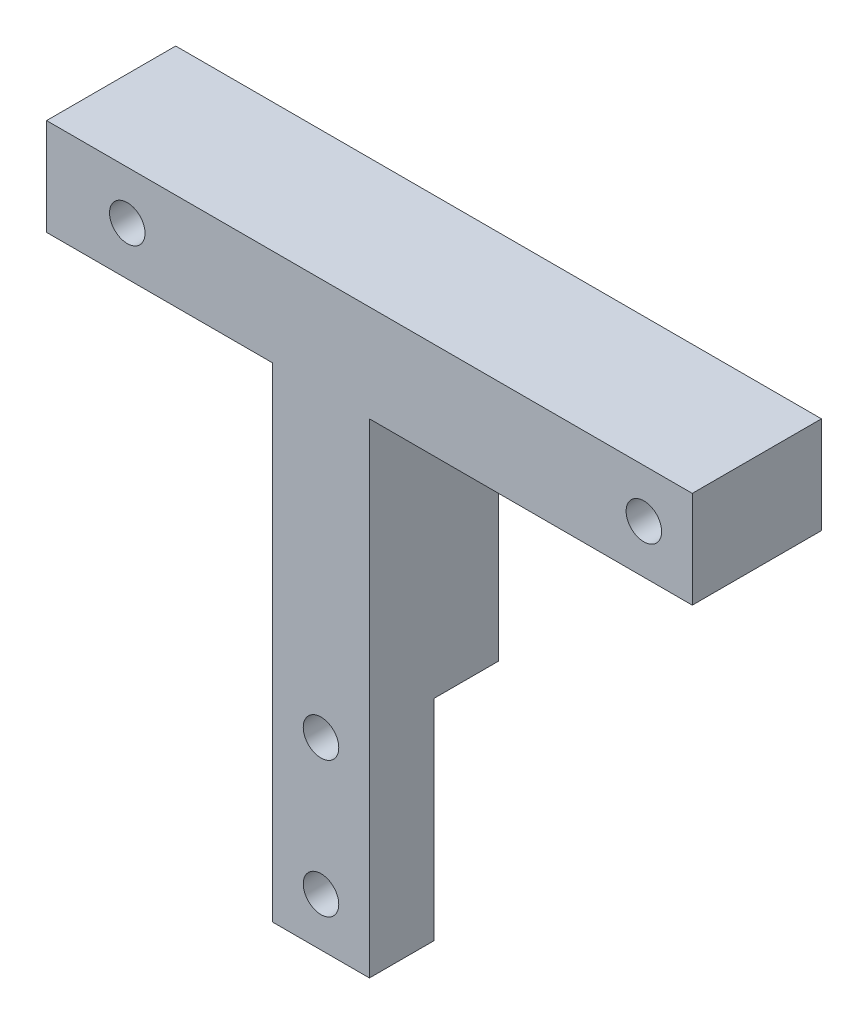
SolidWorks part; units mm, degrees
ref_plane "前视基准面" through (0, 0, 0) normal (0, 0, 1) x (1, 0, 0)
ref_plane "上视基准面" through (0, 0, 0) normal (0, 1, 0) x (1, 0, 0)
ref_plane "右视基准面" through (0, 0, 0) normal (1, 0, 0) x (0, 0, -1)
other "Configuration Table"
sketch "草图1" plane through (0, 0, 0) normal (0, 0, 1) x (1, 0, 0)
  line L0 (0, -1.5) -> (10, -1.5)
  line L1 (-10, 1.5) -> (10, 1.5)
  line L2 (-10, 1.5) -> (-10, -1.5)
  line L3 (-10, -1.5) -> (-3, -1.5)
  line L4 (10, 1.5) -> (10, -1.5)
  line L5 (-10, 1.5) -> (10, -1.5) construction
  line L6 (-10, -1.5) -> (10, 1.5) construction
  line L8 (-3, -1.5) -> (-3, -16.5)
  line L9 (-3, -16.5) -> (0, -16.5)
  line L10 (0, -1.5) -> (0, -16.5)
  circle A0 centre (-7.5, 0) radius 0.55
  circle A1 centre (8.5, 0) radius 0.55
  circle A2 centre (-1.5, -15) radius 0.55
  circle A3 centre (-1.5, -10.8) radius 0.55
  point P0 (0, 0)
  dimension "D5" = 1.1
  dimension "D7" = 1.1
  dimension "D12" = 1.1
  dimension "D13" = 1.1
  dimension "D1" = 20
  dimension "D2" = 3
  dimension "D3" = 3
  dimension "D4" = 15
  dimension "D6" = 2.5
  dimension "D8" = 1.5
  dimension "D9" = 10
  dimension "D10" = 1.5
  dimension "D11" = 1.5
  dimension "D14" = 1.5
  dimension "D15" = 1.5
  dimension "D16" = 1.5
  dimension "D17" = 4.2
extrude "凸台-拉伸2" add sketch "草图1" along normal blind 4
sketch "草图3" plane through (0, 0, 0) normal (0, 0, -1) x (-1, 0, 0)
  line L0 (0, -10) -> (3, -10)
  line L8 (-10, 1.5) -> (-10, -1.5)
  line L9 (-10, -1.5) -> (0, -1.5)
  line L10 (0, -1.5) -> (0, -16.5)
  line L11 (0, -16.5) -> (3, -16.5)
  line L12 (3, -16.5) -> (3, -1.5)
  line L13 (3, -1.5) -> (10, -1.5)
  line L14 (10, -1.5) -> (10, 1.5)
  line L15 (10, 1.5) -> (-10, 1.5)
  line L18 (0, -10) -> (0, -16.5)
  line L19 (0, -16.5) -> (3, -16.5)
  line L20 (3, -16.5) -> (3, -10)
  circle A0 centre (1.5, -15) radius 0.55 construction
  circle A1 centre (1.5, -10.8) radius 0.55 construction
  circle A2 centre (1.5, -15) radius 0.55
  circle A3 centre (1.5, -10.8) radius 0.55
  dimension "D1" = 0
extrude "切除-拉伸2" cut sketch "草图3" against normal blind 2
